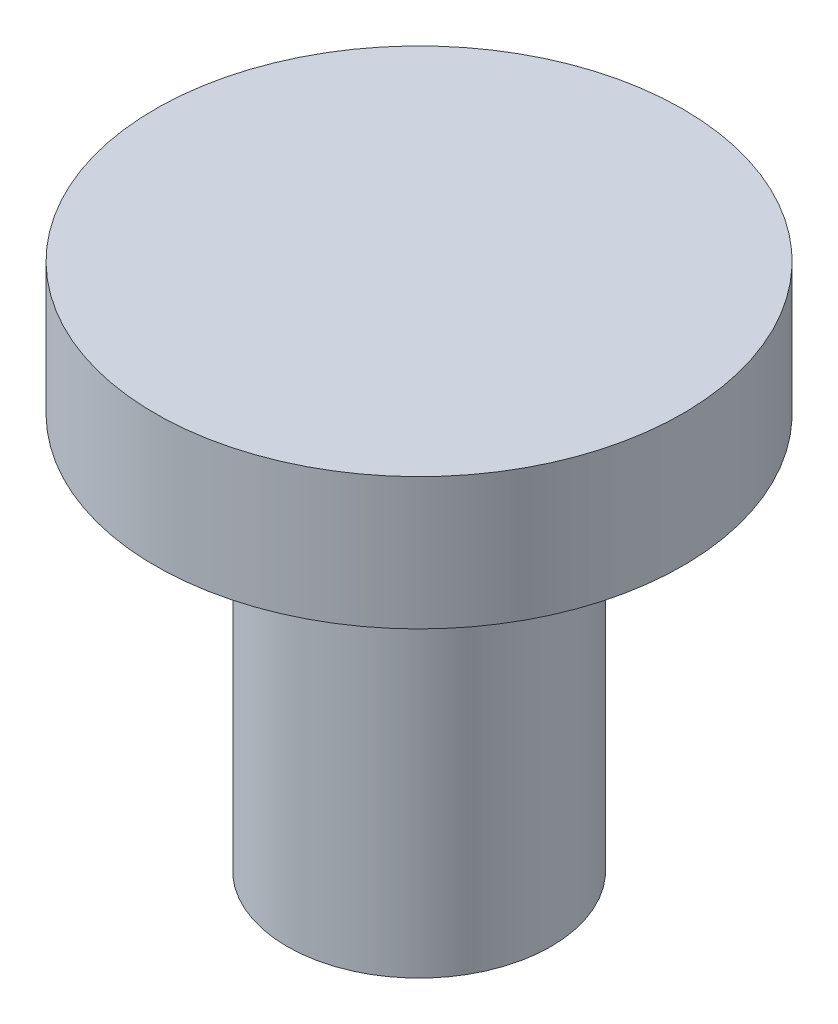
SolidWorks part; units mm, degrees
ref_plane "Front Plane" through (0, 0, 0) normal (0, 0, 1) x (1, 0, 0)
ref_plane "Top Plane" through (0, 0, 0) normal (0, 1, 0) x (1, 0, 0)
ref_plane "Right Plane" through (0, 0, 0) normal (1, 0, 0) x (0, 0, -1)
sketch "Sketch4" plane through (0, 0, 0) normal (0, 0, 1) x (1, 0, 0)
  line L0 (0, 0) -> (0, 4)
  line L1 (0, 4) -> (2, 4)
  line L2 (0, 0) -> (1, 0)
  line L3 (1, 3) -> (1, 0)
  line L4 (2, 4) -> (2, 3)
  line L5 (2, 3) -> (1, 3)
  dimension "D1" = 1
  dimension "D2" = 4
  dimension "D3" = 2
  dimension "D4" = 1
revolve "Revolve1" add sketch "Sketch4" angle 360 about L0
ref_axis "Axis1" through (0, 0, 0) along (0, 1, 0)
